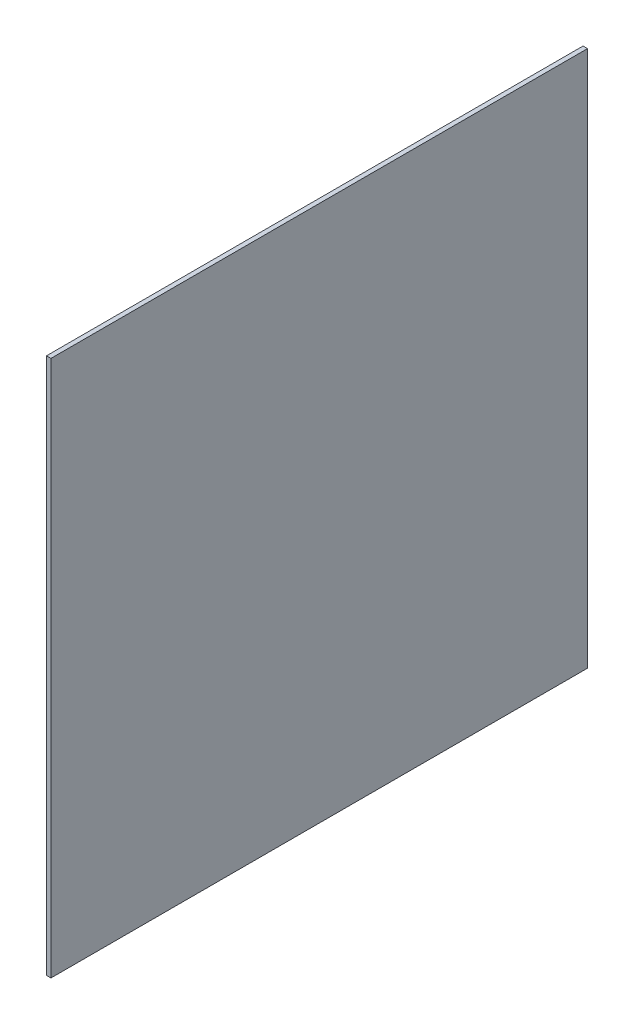
SolidWorks part; units mm, degrees
ref_plane "Front Plane" through (0, 0, 0) normal (0, 0, 1) x (1, 0, 0)
ref_plane "Top Plane" through (0, 0, 0) normal (0, 1, 0) x (1, 0, 0)
ref_plane "Right Plane" through (0, 0, 0) normal (1, 0, 0) x (0, 0, -1)
sketch "Sketch1" plane through (0, 0, 0) normal (1, 0, 0) x (0, 0, -1)
  line L1 (-247.1057, 219.3471) -> (133.8943, 219.3471)
  line L2 (-247.1057, 219.3471) -> (-247.1057, -161.6529)
  line L3 (-247.1057, -161.6529) -> (133.8943, -161.6529)
  line L4 (133.8943, 219.3471) -> (133.8943, -161.6529)
  dimension "D1" = 381
  dimension "D2" = 381
extrude "Boss-Extrude1" add sketch "Sketch1" along normal blind 3.175
